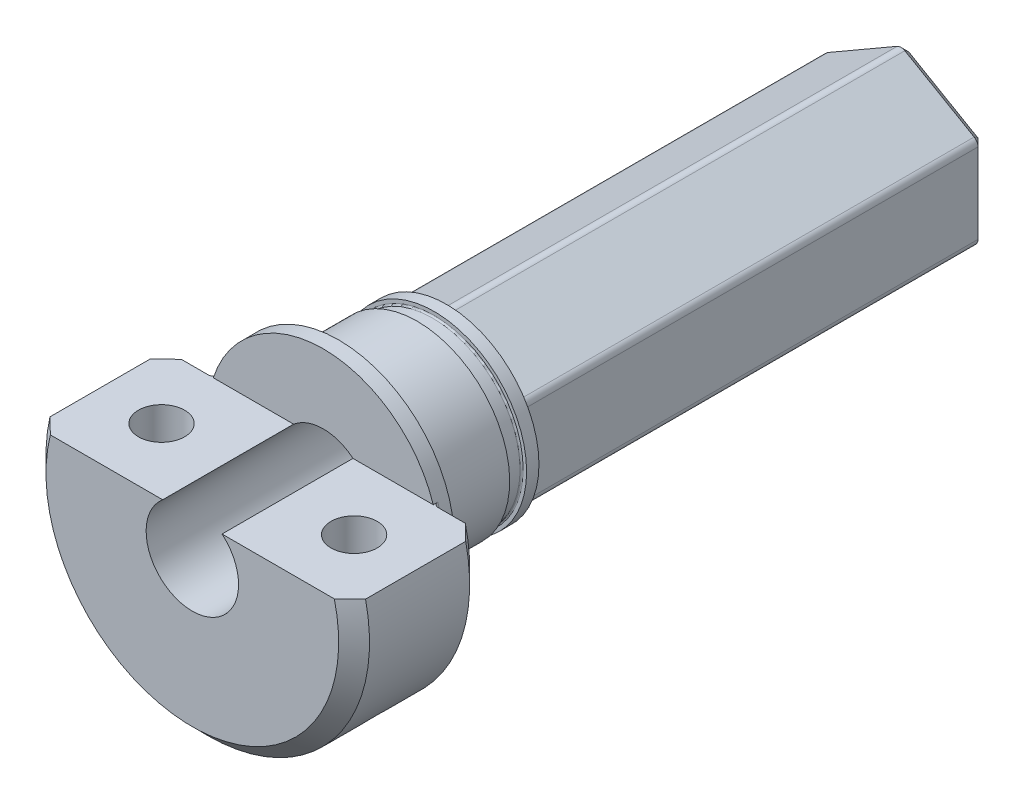
SolidWorks part; units mm, degrees
material "Alloy Steel"
ref_plane "Front" through (0, 0, 0) normal (0, 0, 1) x (1, 0, 0)
ref_plane "Top" through (0, 0, 0) normal (0, 1, 0) x (1, 0, 0)
ref_plane "Right" through (0, 0, 0) normal (1, 0, 0) x (0, 0, -1)
sketch "Sketch1" plane through (0, 0, 0) normal (0, 0, 1) x (1, 0, 0)
  circle A0 centre (0, 0) radius 3
  circle A1 centre (0, 0) radius 10.5
  dimension "D1" = 6
  dimension "D2" = 21
extrude "Extrude1" add sketch "Sketch1" against normal blind 46.5 contours A0 | A1 A0 region at (0, 0, 0) region at (-10.203, 0, 0)
extrude "Cut-Extrude1" cut sketch "Sketch1<3>" against normal through all contours A0 region at (0, 0, 0)
sketch "Sketch1<3>" plane through (0, 0, 0) normal (0, 0, 1) x (1, 0, 0) same geometry as "Sketch1"
sketch "Sketch4" plane through (0, 0, 0) normal (0, 0, 1) x (1, 0, 0)
  line L0 (-10.245, 2.3) -> (10.245, 2.3)
  arc A0 (10.245, 2.3) -> (-10.245, 2.3) centre (0, 0) ccw
  circle A1 centre (0, 0) radius 10.5 construction
  dimension "D1" = 2.3
extrude "Cut-Extrude4" cut sketch "Sketch4" against normal blind 8.5
sketch "Sketch6" plane through (0, 0, -46.5) normal (0, 0, -1) x (1, 0, 0)
  circle A0 centre (0, 0) radius 6
  circle A1 centre (0, 0) radius 10.5
  circle A2 centre (0, 0) radius 10.5 construction
  dimension "D1" = 12
extrude "Cut-Extrude6" cut sketch "Sketch6" against normal offset from surface (37 mm away) 1 up to face at (0, 4.525, -8.5)
sketch "Sketch7" plane through (0, 0, -9.5) normal (0, 0, -1) x (1, 0, 0)
  circle A0 centre (0, 0) radius 10.5
  circle A1 centre (0, 0) radius 7.5
  circle A3 centre (0, 0) radius 10.5 construction
  dimension "D1" = 15
extrude "Cut-Extrude7" cut sketch "Sketch7" against normal blind 1
hole_wizard "M4x0.7 Tapped Hole1" positions "3DSketch1" profile "Sketch10" tap size "M4x0.7" standard "Ansi Metric" end condition through all
sketch3d "3DSketch1"
  line L9 (3, 0, 0) -> (3, 0, -8.5) construction
  line L13 (-3, 0, 0) -> (-3, 0, -8.5) construction
  line L18 (3, 0, 0) -> (10.5, 0, 0) construction
  line L20 (-3, 0, 0) -> (-10.5, 0, 0) construction
  line L25 (6.25, 0, 0) -> (6.25, 0, -8.5) construction
  line L26 (3, 0, -8.5) -> (10.5, 0, -8.5) construction
  line L27 (-3, 0, -8.5) -> (-10.5, 0, -8.5) construction
  line L30 (-6.25, 0, 0) -> (-6.25, 0, -8.5) construction
  arc A1 (-1.9261, 2.3, 0) -> (1.9261, 2.3, 0) centre (0, 0, 0) ccw construction
  arc A2 (-10.245, 2.3, 0) -> (10.245, 2.3, 0) centre (0, 0, 0) ccw construction
  point P0 (6.25, 2.3, -4.25)
  point P2 (-6.25, 2.3, -4.25)
  point P33 (0, 0, 3)
  point P54 (0, 0, 10.5)
  point P93 (6.25, 0, -4.25)
  point P118 (-6.25, 0, -4.25)
  dimension "D1" = 6.25
  dimension "D2" = 6.25
sketch "Sketch10" plane through (6.25, 2.3, -4.25) normal (1, 0, 0) x (0, 0, 1)
  line L0 (0, 0) -> (0, 12.8)
  line L1 (0, 12.8) -> (1.5, 12.8)
  line L2 (1.5, 12.8) -> (1.5, 0)
  line L5 (1.5, 0) -> (0, 0)
  line L11 (0, -6.35) -> (0, 107.95) construction
  dimension "Thru Tap Drill Dia." = 3
  dimension "Thru Tap Drill Depth" = 12.8
cosmetic thread "Hole Thread3"
cosmetic thread "Hole Thread4"
sketch "Sketch8" plane through (0, 0, -46.5) normal (0, 0, -1) x (1, 0, 0)
  line L0 (0, 0) -> (0, 16.2426) construction
  line L1 (0, 5.7735) -> (-5, 2.8868)
  line L2 (-5, 2.8868) -> (-5, -2.8868)
  line L3 (-5, -2.8868) -> (0, -5.7735)
  line L4 (0, -5.7735) -> (5, -2.8868)
  line L5 (5, -2.8868) -> (5, 2.8868)
  line L6 (5, 2.8868) -> (0, 5.7735)
  circle A0 centre (0, 0) radius 5 construction
  dimension "D1" = 10
extrude "Cut-Extrude8" cut sketch "Sketch8" against normal offset from surface (30 mm away) 7 flip side to cut up to face at (6, 0, -9.5)
fillet "Fillet1" radius 0.5 6 edges at (-5, -2.8868, -31.5) (-5, 2.8868, -31.5) (0, 5.7735, -31.5) (5, 2.8868, -31.5) (5, -2.8868, -31.5) (0, -5.7735, -31.5)
chamfer "Chamfer1" distance 0.5 angle 45 12 edges at (-5, 0, -46.5) (-2.5, 4.3301, -46.5) (2.5, 4.3301, -46.5) (5, 0, -46.5) (2.5, -4.3301, -46.5) (4.933, 2.8481, -46.5) (0, 5.6962, -46.5) (4.933, -2.8481, -46.5) (-4.933, 2.8481, -46.5) (0, -5.6962, -46.5) (-4.933, -2.8481, -46.5) (-2.5, -4.3301, -46.5)
ref_plane "Plane1" through (0, 0, 19.3701) normal (-1, 0, 0) x (0, 1, 0)
sketch "Sketch12" plane through (0, 0, 19.3701) normal (-1, 0, 0) x (0, 1, 0)
  line L0 (5.775, 33.9701) -> (7.275, 33.9701)
  line L1 (7.275, 33.9701) -> (7.275, 35.0701)
  line L2 (7.275, 35.0701) -> (5.775, 35.0701)
  line L3 (5.675, 34.9701) -> (5.675, 34.0701)
  line L4 (0, -49.9891) -> (0, 54.8742) construction
  line L5 (7.5, 28.8701) -> (-7.5, 28.8701) construction
  line L8 (3, 65.8701) -> (-3, 65.8701) construction
  arc A0 (5.675, 34.0701) -> (5.775, 33.9701) centre (5.775, 34.0701) ccw
  arc A1 (5.675, 34.9701) -> (5.775, 35.0701) centre (5.775, 34.9701) cw
  point P14 (0, 65.8701)
  dimension "D1" = 0.1
  dimension "D2" = 0.1
  dimension "D3" = 5.1
  dimension "D4" = 5.675
  dimension "D5" = 1.1
  dimension "D6" = 1.5
revolve "Groove for ANSI B27.7 - 3AM1-12, Basic External Retaining Ring1" cut sketch "Sketch12"
fillet "Fillet2" radius 0.3 2 edges at (6, 0, -9.5) (0, -7.5, -8.5)
chamfer "Chamfer2" distance 1 angle 45 2 edges at (0, -10.5, -8.5) (0, -10.5, 0)
